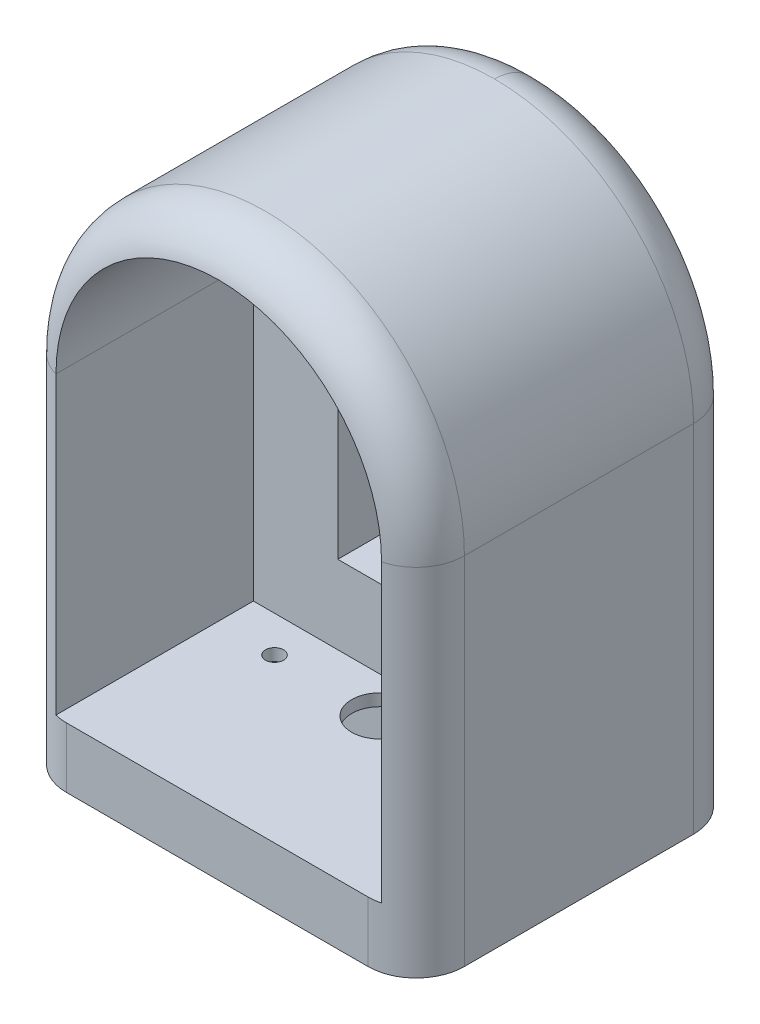
SolidWorks part; units mm, degrees
ref_plane "Front Plane" through (0, 0, 0) normal (0, 0, 1) x (1, 0, 0)
ref_plane "Top Plane" through (0, 0, 0) normal (0, 1, 0) x (1, 0, 0)
ref_plane "Right Plane" through (0, 0, 0) normal (1, 0, 0) x (0, 0, -1)
sketch "Sketch1" plane through (0, 0, 0) normal (0, 1, 0) x (1, 0, 0)
  line L1 (-16.5, -13.5) -> (16.5, -13.5)
  line L2 (-16.5, -13.5) -> (-16.5, 13.5)
  line L3 (-16.5, 13.5) -> (16.5, 13.5)
  line L4 (16.5, -13.5) -> (16.5, 13.5)
  line L5 (-16.5, -13.5) -> (16.5, 13.5) construction
  line L6 (-16.5, 13.5) -> (16.5, -13.5) construction
  point P0 (0, 0)
  dimension "D1" = 33
  dimension "D2" = 27
extrude "Boss-Extrude1" add sketch "Sketch1" along normal blind 46
sketch "Sketch3" plane through (16.5, 0, 0) normal (1, 0, 0) x (0, 0, -1)
  line L2 (-13.5, 0) -> (13.5, 0) construction
  line L3 (13.5, 46) -> (11, 46)
  line L4 (13.5, 46) -> (13.5, 21)
  line L5 (13.5, 21) -> (11, 21)
  line L6 (11, 46) -> (11, 21)
  line L7 (-13.5, 46) -> (3, 46)
  line L8 (-13.5, 46) -> (-13.5, 5)
  line L9 (-13.5, 5) -> (3, 5)
  line L10 (3, 46) -> (3, 5)
  line M11 (13.5, 46) -> (-13.5, 46)
  line M12 (-13.5, 46) -> (-13.5, 0)
  dimension "D1" = 5
  dimension "D2" = 8
  dimension "D3" = 2.5
  dimension "D4" = 25
extrude "Cut-Extrude2" cut sketch "Sketch3" against normal through all contours L10 L9 M11 M12 region at (16.5, 25.5, 5.25)
sketch "Sketch4" plane through (0, 0, 0) normal (0, -1, 0) x (1, 0, 0)
  line L0 (-16.5, -13.5) -> (-16.5, 13.5) construction
  line L1 (0, 0) -> (14, 0)
  line L2 (0.1339, 2.4964) -> (14.0938, 1.7475)
  line L3 (0.1339, -2.4964) -> (14.0938, -1.7475)
  line L4 (0, 0) -> (0, 2.5)
  line L5 (-0.1339, -2.4964) -> (-14.0938, -1.7475)
  line L6 (-0.1339, 2.4964) -> (-14.0938, 1.7475)
  arc A0 (0.1339, 2.4964) -> (-0.1339, 2.4964) centre (0, 0) ccw
  arc A1 (14.0938, -1.7475) -> (14.0938, 1.7475) centre (14, 0) ccw
  arc A2 (-14.0938, -1.7475) -> (-14.0938, 1.7475) centre (-14, 0) cw
  arc A3 (-0.1339, -2.4964) -> (0.1339, -2.4964) centre (0, 0) ccw
  dimension "D2" = 5
  dimension "D1" = 16.5
fillet "Fillet3" radius 16.5 2 edges at (-16.5, 46, -8.25) (16.5, 46, -8.25)
sketch "Sketch9" plane through (0, 0, -3) normal (0, 0, 1) x (1, 0, 0)
  line L0 (-16.5, 5) -> (16.5, 5) construction
  line L1 (-6.5, 11.5) -> (6.5, 11.5)
  line L2 (-6.5, 11.5) -> (-6.5, 34.5)
  line L3 (-6.5, 34.5) -> (6.5, 34.5)
  line L4 (6.5, 11.5) -> (6.5, 34.5)
  line L5 (-6.5, 11.5) -> (6.5, 34.5) construction
  line L6 (-6.5, 34.5) -> (6.5, 11.5) construction
  point P0 (0, 23)
  dimension "D1" = 13
  dimension "D2" = 23
  dimension "D3" = 6.5
extrude "Cut-Extrude4" cut sketch "Sketch9" against normal blind 9
sketch "Sketch10" plane through (0, 0, -12) normal (0, 0, 1) x (1, 0, 0)
  line L1 (6.5, 34.5) -> (-6.5, 34.5) construction
  circle A0 centre (0, 28) radius 6.5
  dimension "D1" = 13
  dimension "D2" = 6.5
extrude "Cut-Extrude5" cut sketch "Sketch10" against normal through all
sketch "Sketch11" plane through (0, 0, -3) normal (0, 0, 1) x (1, 0, 0)
  line L1 (6.5, 34.5) -> (0, 34.5) construction
  circle A0 centre (0, 36.8) radius 1
  circle A1 centre (0, 9.2) radius 1
  dimension "D1" = 27.6
  dimension "D2" = 2
  dimension "D3" = 2
  dimension "D4" = 2.3
extrude "Cut-Extrude6" cut sketch "Sketch11" against normal blind 8
sketch "Sketch15" plane through (0, 0, -3) normal (0, 0, 1) x (1, 0, 0)
  line L3 (13.5, 5) -> (13.5, 29.5)
  line L4 (13.5, 5) -> (13.5, 29.5)
  line L5 (16.5, 5) -> (16.5, 29.5)
  line L6 (-13.5, 29.5) -> (-13.5, 5)
  line L7 (-13.5, 29.5) -> (-13.5, 5)
  line L8 (-16.5, 29.5) -> (-16.5, 5)
  line L9 (-16.5, 5) -> (-13.5, 5)
  line L10 (13.5, 5) -> (16.5, 5)
  arc A11 (16.5, 29.5) -> (0, 46) centre (0, 29.5) ccw
  arc A12 (0, 46) -> (-16.5, 29.5) centre (0, 29.5) ccw
  arc A13 (13.5, 29.5) -> (0, 43) centre (0, 29.5) ccw
  arc A14 (0, 43) -> (-13.5, 29.5) centre (0, 29.5) ccw
  arc A15 (13.5, 29.5) -> (0, 43) centre (0, 29.5) ccw
  arc A16 (0, 43) -> (-13.5, 29.5) centre (0, 29.5) ccw
  dimension "D1" = 3
  dimension "D2" = 3
  dimension "D3" = 3
extrude "Boss-Extrude7" add sketch "Sketch15" along normal blind 16.5
fillet "Fillet5" radius 4 6 edges at (16.5, 14.75, 13.5) (-16.5, 14.75, 13.5) (-16.5, 14.75, -13.5) (16.5, 14.75, -13.5) (11.6673, 41.1673, -13.5) (-11.6673, 41.1673, -13.5)
extrude "Cut-Extrude7" cut sketch "Sketch4" against normal blind 4 contours L5 A3 L3 A1 L2 A0 L6 A2 region at (7.0968, 0, 1.8035)
sketch "Sketch17" plane through (0, 4, 0) normal (0, -1, 0) x (1, 0, 0)
  circle A0 centre (0, 0) radius 1.3
extrude "Cut-Extrude8" cut sketch "Sketch17" against normal blind 1.75
sketch "Sketch18" plane through (0, 5, 0) normal (0, 1, 0) x (1, 0, 0)
  circle A0 centre (0, 0) radius 2.35
extrude "Cut-Extrude9" cut sketch "Sketch18" against normal blind 1
sketch "Sketch19" plane through (0, 4, 0) normal (0, -1, 0) x (1, 0, 0)
  line L0 (0, 0) -> (-8, 0)
  line L1 (0, 0) -> (8, 0)
  circle A2 centre (-8.75, 0) radius 0.75
  circle A3 centre (8.75, 0) radius 0.75
  point P11 (0, 0)
  point P12 (0, 0)
  point P15 (0, 0)
extrude "Cut-Extrude10" cut sketch "Sketch19" against normal blind 1.75 contours A2 | A3 region at (-8.75, 4, 0)
